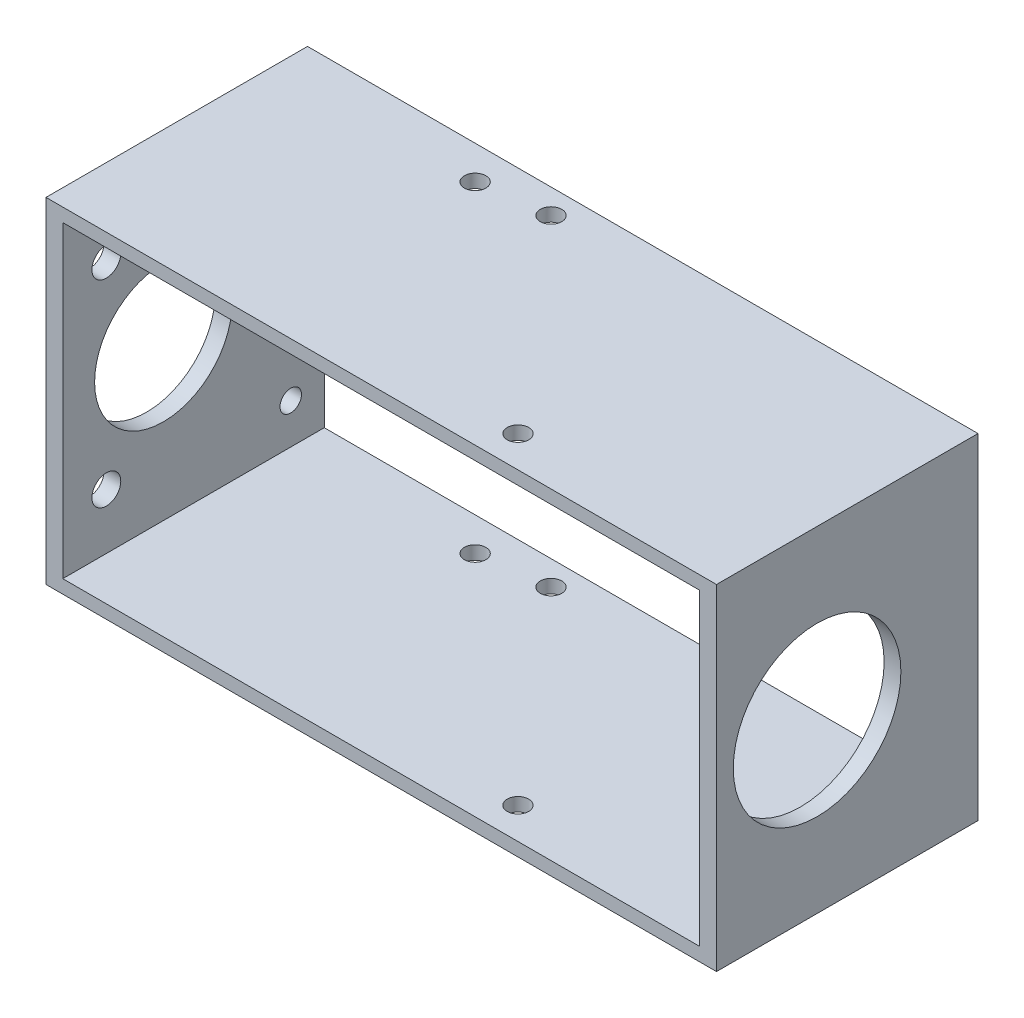
SolidWorks part; units mm, degrees
ref_plane "正面" through (0, 0, 0) normal (0, 0, 1) x (1, 0, 0)
ref_plane "平面" through (0, 0, 0) normal (0, 1, 0) x (1, 0, 0)
ref_plane "右側面" through (0, 0, 0) normal (1, 0, 0) x (0, 0, -1)
sketch "ｽｹｯﾁ1" plane through (0, 0, 0) normal (0, 0, 1) x (1, 0, 0)
  line L1 (-50, -25) -> (50, -25)
  line L2 (-50, -25) -> (-50, 25)
  line L3 (-50, 25) -> (50, 25)
  line L4 (50, -25) -> (50, 25)
  line L5 (-50, -25) -> (50, 25) construction
  line L6 (-50, 25) -> (50, -25) construction
  line L7 (-47.5, -23) -> (47.5, -23)
  line L8 (-47.5, -23) -> (-47.5, 23)
  line L9 (-47.5, 23) -> (47.5, 23)
  line L10 (47.5, -23) -> (47.5, 23)
  line L11 (-47.5, -23) -> (47.5, 23) construction
  line L12 (-47.5, 23) -> (47.5, -23) construction
  point P0 (0, 0)
  point P6 (0, 0)
  dimension "D1" = 2
  dimension "D2" = 2.5
  dimension "D3" = 50
  dimension "D4" = 100
extrude "ﾎﾞｽ - 押し出し1" add sketch "ｽｹｯﾁ1" along normal mid plane 39
sketch "ｽｹｯﾁ2" plane through (0, 25, 0) normal (0, 1, 0) x (1, 0, 0)
  line L0 (-10, 15.8209) -> (15.7115, -14.8209) construction
  line L1 (2.8558, 0.5) -> (50, 0.5) construction
  line L2 (50, -19.5) -> (50, 19.5) construction
  line L3 (50, -19.5) -> (-50, -19.5) construction
  line L4 (-50, -19.5) -> (-50, 19.5) construction
  line L5 (50, 19.5) -> (-50, 19.5) construction
  circle A0 centre (-10, 15.8209) radius 1.6
  circle A1 centre (15.7115, -14.8209) radius 1.6
  circle A2 centre (-20, 14.5) radius 1.6
  dimension "D2" = 3.2
  dimension "D6" = 30
  dimension "D7" = 5
  dimension "D5" = 60
  dimension "D1" = 40
  dimension "D3" = 20
  dimension "D4" = 50
extrude "ｶｯﾄ - 押し出し1" cut sketch "ｽｹｯﾁ2" against normal through all
sketch "ｽｹｯﾁ3" plane through (-50, 0, 0) normal (-1, 0, 0) x (0, 0, 1)
  line L0 (4.5, 0) -> (4.5, 21.5) construction
  line L1 (19.5, 25) -> (19.5, -25) construction
  line L2 (-30.7, -9) -> (-30.7, 9) construction
  line L3 (21.45, 0) -> (-21.45, 0) construction
  line L4 (-12.5, 0) -> (4.5, 0) construction
  line L5 (-14.5, -17) -> (-14.5, 17) construction
  line L6 (19.5, 25) -> (-19.5, 25) construction
  line L7 (-19.5, 25) -> (-19.5, -25) construction
  circle A0 centre (4.5, 0) radius 21.5 construction
  circle A1 centre (4.5, 0) radius 10.25
  circle A3 centre (-30.7, 0) radius 6.05 construction
  circle A4 centre (-30.7, -9) radius 1.6 construction
  circle A5 centre (-30.7, 9) radius 1.6 construction
  circle A8 centre (-12.5, 0) radius 2.15
  circle A9 centre (4.5, 0) radius 17 construction
  circle A10 centre (13, 14.7224) radius 2.15
  circle A11 centre (13, -14.7224) radius 2.15
  circle A12 centre (-14.5, -17) radius 1.6
  circle A13 centre (-14.5, 17) radius 1.6
  point P12 (-30.7, 0)
  point P18 (-14.5, 0)
  point P21 (4.5, 0)
  point P28 (4.5, 0)
  dimension "D1" = 43
  dimension "D3" = 20.5
  dimension "D6" = 3.2
  dimension "D8" = 12.1
  dimension "D4" = 4.3
  dimension "D10" = 34
  dimension "D2" = 3.2
  dimension "D5" = 15
  dimension "D7" = 18
  dimension "D9" = 35.2
  dimension "D12" = 8
  dimension "D13" = 5
  dimension "D11" = 3
extrude "ｶｯﾄ - 押し出し2" cut sketch "ｽｹｯﾁ3" against normal up to next
sketch "ｽｹｯﾁ4" plane through (50, 0, 0) normal (1, 0, 0) x (0, 0, -1)
  circle A0 centre (-4.5, 0) radius 12.5
  circle A1 centre (-4.5, 0) radius 10.25 construction
  dimension "D1" = 25
extrude "ｶｯﾄ - 押し出し3" cut sketch "ｽｹｯﾁ4" against normal up to next
equation "\"D9@ｽｹｯﾁ3\"=(66+22)*0.8/2"
